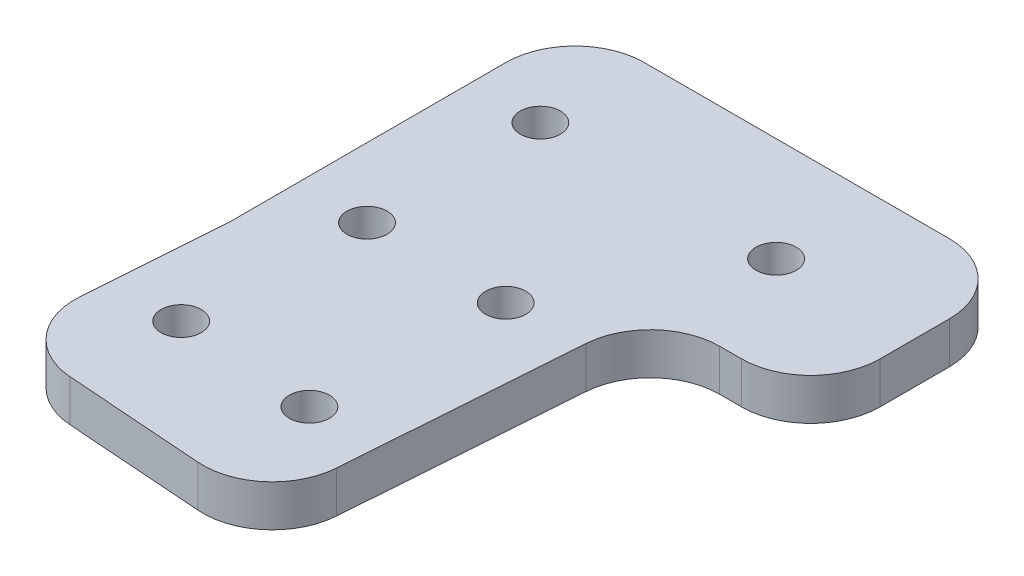
SolidWorks part; units mm, degrees
material "Thornel Mat VMA"
ref_plane "前视基准面" through (0, 0, 0) normal (0, 0, 1) x (1, 0, 0)
ref_plane "上视基准面" through (0, 0, 0) normal (0, 1, 0) x (1, 0, 0)
ref_plane "右视基准面" through (0, 0, 0) normal (1, 0, 0) x (0, 0, -1)
other "Configuration Table"
sketch "草图1" plane through (0, 0, 0) normal (0, 1, 0) x (1, 0, 0)
  line L0 (0, -10) -> (-1.0892, -24.9604) construction
  line L1 (0, 0) -> (680, 0) construction
  line L2 (0, 0) -> (0, 15) construction
  line L3 (0, 15) -> (680, 15) construction
  line L4 (680, 0) -> (680, 15) construction
  line L5 (0, -10) -> (680, -59.51) construction
  line L6 (-1.0892, -24.9604) -> (678.9108, -74.4704) construction
  line L7 (680, -59.51) -> (678.9108, -74.4704) construction
  line L8 (0, 0) -> (0, -10)
  line L9 (0, -10) -> (19.9472, -11.4523) construction
  line L10 (19.9472, -11.4523) -> (20.781, 0)
  line L11 (20.781, 0) -> (0, 0) construction
  line L12 (654.2534, 0) -> (650.0792, -57.3315) construction
  line L13 (650.0792, -57.3315) -> (680, -59.51) construction
  line L14 (680, -59.51) -> (680, 0) construction
  line L15 (680, 0) -> (654.2534, 0) construction
  line L16 (570.2904, -51.5222) -> (571.6245, -33.1995) construction
  line L17 (570.2904, -51.5222) -> (-45.7125, -51.5222) construction
  line L18 (0, 0) -> (0, 15)
  line L19 (0, 15) -> (20.781, 15)
  line L20 (20.781, 15) -> (20.781, 0) construction
  line L21 (19.9472, -11.4523) -> (18.8579, -26.4127)
  line L22 (18.8579, -26.4127) -> (-1.0892, -24.9604)
  line L23 (-1.0892, -24.9604) -> (0, -10)
  line L24 (-9.6905, 7.5) -> (55.8818, 7.5) construction
  line L25 (-13.1883, -16.5596) -> (73.1713, -22.8474) construction
  line L26 (5, -5) -> (15, -5) construction
  line L27 (20.781, 15) -> (32, 15)
  line L28 (32, 15) -> (32, 0)
  line L29 (32, 0) -> (20.781, 0)
  circle A0 centre (5, 7.5) radius 1.45
  circle A1 centre (22, 7.5) radius 1.45
  circle A2 centre (4.4422, -17.8433) radius 1.45
  circle A3 centre (14.4158, -18.5694) radius 1.45
  circle A4 centre (5, -5) radius 1.45
  circle A5 centre (15, -5) radius 1.45
  dimension "D11" = 2.9
  dimension "D13" = 17
  dimension "D14" = 5
  dimension "D15" = 5
  dimension "D16" = 5
  dimension "D17" = 10
  dimension "D18" = 5
  dimension "D19" = 10
  dimension "D1" = 15
  dimension "D2" = 15
  dimension "D3" = 680
  dimension "D4" = 20
  dimension "D5" = 80
  dimension "D6" = 681.8
  dimension "D7" = 30
  dimension "D8" = 10
  dimension "D9" = 7.5
  dimension "D10" = 7.5
  dimension "D12" = 5
extrude "凸台-拉伸1" add sketch "草图1" along normal blind 3
fillet "圆角1" radius 5 7 edges at (0, 1.5, -15) (18.8579, 1.5, 26.4127) (-1.0892, 1.5, 24.9604) (0, 1.5, 10) (32, 1.5, -15) (32, 1.5, 0) (20.781, 1.5, 0)
